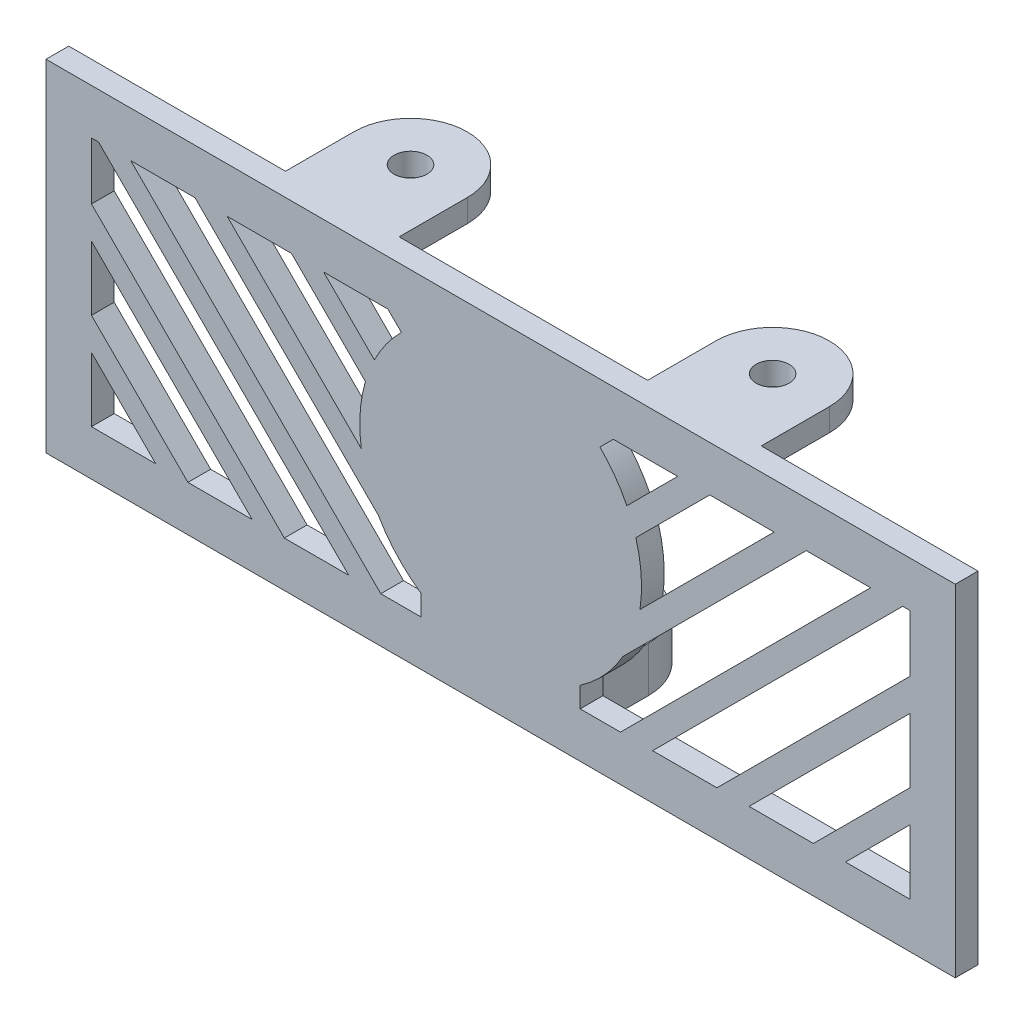
SolidWorks part; units mm, degrees
ref_plane "Front Plane" through (0, 0, 0) normal (0, 0, 1) x (1, 0, 0)
ref_plane "Top Plane" through (0, 0, 0) normal (0, 1, 0) x (1, 0, 0)
ref_plane "Right Plane" through (0, 0, 0) normal (1, 0, 0) x (0, 0, -1)
sketch "Sketch1" plane through (0, 0, 0) normal (0, 1, 0) x (1, 0, 0)
  line L0 (100.8063, 0) -> (100.8063, -127) construction
  line L1 (0, 0) -> (201.6125, 0)
  line L2 (0, 0) -> (0, -45.847)
  line L3 (0, -45.847) -> (34.944, -45.847)
  line L9 (19.05, -7.62) -> (182.5625, -7.62)
  line L10 (19.05, -7.62) -> (19.05, -38.2238)
  line L11 (19.05, -38.2238) -> (182.5625, -38.2238)
  line L12 (182.5625, -7.62) -> (182.5625, -38.2238)
  line L13 (60.344, -58.547) -> (73.2151, -58.547) construction
  line L14 (141.2685, -58.547) -> (171.549, -58.547) construction
  line L15 (74.2236, -72.4265) -> (74.2236, -91.8023) construction
  line L16 (127.3874, -72.4281) -> (127.3874, -64.5576) construction
  line L17 (166.6685, -45.847) -> (201.6125, -45.847)
  line L18 (182.5625, -22.9219) -> (-7.7585, -22.9219) construction
  line L22 (201.6125, 0) -> (201.6125, -45.847)
  line L29 (34.944, -45.847) -> (34.9441, -83.7692)
  line L30 (100.8063, -127) -> (100.8063, -142.2501) construction
  line L32 (166.6685, -45.847) -> (166.6685, -83.7692)
  line L34 (114.6874, -72.4281) -> (114.6874, -88.9176) construction
  line L35 (100.8063, -58.547) -> (112.2464, -58.547) construction
  line L36 (50.1841, -99.0092) -> (151.4284, -99.0092)
  line L37 (141.2685, -86.3092) -> (149.6169, -86.3092) construction
  circle A0 centre (60.344, -72.4265) radius 13.8795
  circle A1 centre (141.2685, -72.4281) radius 13.8811
  circle A2 centre (13.0969, -9.7139) radius 2.54
  circle A3 centre (188.5156, -9.7139) radius 2.54
  circle A4 centre (13.0969, -36.1299) radius 2.54
  circle A5 centre (188.5156, -36.1299) radius 2.54
  circle A10 centre (100.8063, -72.4281) radius 13.8811
  arc A23 (151.4284, -99.0092) -> (166.6685, -83.7692) centre (151.4285, -83.7692) ccw
  arc A24 (50.1841, -99.0092) -> (34.9441, -83.7692) centre (50.184, -83.7692) cw
  point P48 (166.6685, -99.0092)
  point P51 (34.9441, -99.0092)
  dimension "D7" = 27.759
  dimension "D16" = 5.08
  dimension "D33" = 27.7622
  dimension "D21" = 27.7622
  dimension "D22" = 15.24
  dimension "D1" = 201.6125
  dimension "D2" = 30.6038
  dimension "D3" = 163.5125
  dimension "D4" = 19.05
  dimension "D5" = 45.847
  dimension "D6" = 7.62
  dimension "D9" = 12.7
  dimension "D14" = 175.4187
  dimension "D15" = 87.7094
  dimension "D17" = 26.416
  dimension "D18" = 13.208
  dimension "D19" = 26.416
  dimension "D20" = 13.208
  dimension "D8" = 25.4
  dimension "D10" = 12.7
  dimension "D11" = 25.4
  dimension "D12" = 12.7
  dimension "D13" = 12.7
extrude "Boss-Extrude1" add sketch "Sketch1" along normal blind 5.08
sketch "Sketch3" plane through (0, 0, 198.0184) normal (0, 1, 0) x (-1, 0, 0)
  line L12 (-50.1841, -99.0092) -> (-151.4284, -99.0092) construction
  line L14 (-50.0063, -101.5492) -> (-151.6062, -101.5492)
  line L21 (-50.0063, -101.5492) -> (-50.0063, -99.0092)
  line L22 (-50.0063, -99.0092) -> (-151.6062, -99.0092)
  line L23 (-151.6062, -99.0092) -> (-151.6062, -101.5492)
  point P3 (-100.8063, -101.5492)
  point P7 (-100.8063, -99.0092)
  point P10 (-100.8063, -99.0092)
  dimension "D1" = 101.6
  dimension "D2" = 2.54
extrude "Boss-Extrude4" add sketch "Sketch3" against normal blind 38.1
sketch "Sketch7" plane through (0, 0, 99.0092) normal (0, 0, -1) x (1, 0, 0)
  line L1 (96.9962, 33.02) -> (104.6162, 33.02)
  line L2 (96.9962, 33.02) -> (96.9962, 38.1)
  line L3 (96.9962, 38.1) -> (104.6162, 38.1)
  line L4 (104.6162, 33.02) -> (104.6162, 38.1)
  line L7 (151.6062, 38.1) -> (151.6062, 0) construction
  line L9 (50.0063, 38.1) -> (151.6062, 38.1) construction
  dimension "D1" = 46.99
  dimension "D2" = 7.62
  dimension "D3" = 5.08
  dimension "D4" = 0
extrude "Boss-Extrude5" add sketch "Sketch7" along normal blind 11.43
fillet "Fillet5" 2 edges at (104.6162, -35.56, 87.5792) (96.9962, -35.56, 87.5792) type full round first side face at (104.6162, -35.56, 92.0242) second side face at (96.9962, -35.56, 92.0242) middle face at (100.8062, -35.56, 87.5792)
sketch "Sketch12" plane through (201.6125, 0, 0) normal (1, 0, 0) x (0, 0, -1)
  line L2 (0, 0) -> (-155.0308, 0)
  line L3 (0, 0) -> (0, 26.8372)
  line L4 (0, 26.8372) -> (-155.0308, 26.8372)
  line L5 (-155.0308, 0) -> (-155.0308, 26.8372)
sketch "Sketch14" plane through (0, 0, 99.0092) normal (0, 0, -1) x (-1, 0, 0)
  line L0 (199.3383, 310.1514) -> (657.3383, 310.1514) construction
  line L1 (-106.6923, -23.8525) -> (-108.1651, -25.3252)
  line L2 (-94.3545, -23.0235) -> (-92.9253, -24.8077)
  line L3 (-109.3118, -20.69) -> (-109.3118, -12.0094)
  line L4 (-92.301, -20.69) -> (-92.301, -12.0094)
  line L5 (-100.8062, -23.2208) -> (-99.5994, -22.3806)
  line L6 (-99.5994, -22.3806) -> (-99.5994, -18.3831)
  line L7 (-99.5994, -18.3831) -> (-94.428, -16.0226)
  line L8 (-94.428, -16.0226) -> (-95.2573, -18.7163)
  line L9 (-95.2573, -18.7163) -> (-98.169, -19.0875)
  line L10 (-98.169, -19.0875) -> (-98.169, -30.8772)
  line L11 (-98.169, -30.8772) -> (-98.1134, -30.8772)
  line L12 (-93.3803, -21.1933) -> (-93.3803, -12.3078)
  line L13 (-103.4991, -30.8772) -> (-103.4435, -30.8772)
  line L14 (-108.2322, -21.1933) -> (-108.2322, -12.3078)
  line L15 (-107.1845, -16.0226) -> (-106.3552, -18.7163)
  line L16 (-106.3552, -18.7163) -> (-103.4435, -19.0875)
  line L17 (-102.0131, -18.3831) -> (-107.1845, -16.0226)
  line L18 (-102.0131, -22.3806) -> (-102.0131, -18.3831)
  line L19 (-100.8062, -23.2208) -> (-102.0131, -22.3806)
  line L20 (-103.4435, -19.0875) -> (-103.4435, -30.8772)
  line L21 (-109.188, -24.2376) -> (-111.0162, -25.7334)
  line L22 (-110.6636, -21.8648) -> (-112.8137, -22.8431)
  line L23 (-90.6831, -21.2276) -> (-88.475, -22.0669)
  line L24 (-90.0847, -25.0658) -> (-92.0045, -23.6895)
  line L25 (-100.8062, -23.2208) -> (-100.8062, -7.3481) construction
  line L26 (-100.8062, -6.8497) -> (-100.8062, -4.1876) construction
  line L27 (-111.494, -19.1279) -> (-113.8252, -19.5092)
  line L28 (-111.5856, -16.3352) -> (-113.9368, -16.1074)
  line L29 (-110.9363, -13.5498) -> (-113.1458, -12.7144)
  line L30 (-109.6192, -11.0855) -> (-111.5415, -9.7126)
  line L31 (-107.6642, -8.9979) -> (-109.16, -7.1697)
  line L32 (-105.2914, -7.5223) -> (-106.2698, -5.3722)
  line L33 (-102.5545, -6.6919) -> (-102.9358, -4.3606)
  line L34 (-99.7619, -6.6003) -> (-99.5341, -4.2491)
  line L35 (-96.9764, -7.2496) -> (-96.141, -5.0401)
  line L36 (-94.5121, -8.5667) -> (-93.1392, -6.6444)
  line L37 (-92.4245, -10.5217) -> (-90.5963, -9.0259)
  line L38 (-90.9489, -12.8944) -> (-88.7988, -11.9161)
  line L39 (-90.1185, -15.6314) -> (-87.7873, -15.2501)
  line L40 (-90.0269, -18.424) -> (-87.6757, -18.6518)
  line L42 (-151.6062, -38.1) -> (-151.6062, 0) construction
  line L49 (-107.1004, -26.1926) -> (-108.4733, -28.1149) [skipped]
  line L50 (-104.6361, -27.5096) -> (-105.4715, -29.7192) [skipped]
  line L51 (-101.8506, -28.159) -> (-102.0784, -30.5102) [skipped]
  line L52 (-99.058, -28.0674) -> (-98.6767, -30.3986) [skipped]
  line L53 (-96.3211, -27.237) -> (-95.3427, -29.3871) [skipped]
  line L54 (-93.9483, -25.7614) -> (-92.4525, -27.5896) [skipped]
  line L55 (-90.6762, -21.2095) -> (-88.4667, -22.0449) [skipped]
  line L56 (-91.9933, -23.6738) -> (-90.071, -25.0466) [skipped]
  arc A0 (-108.1651, -25.3252) -> (-109.188, -24.2376) centre (-100.8062, -17.3796) cw
  arc A1 (-106.6923, -23.8525) -> (-109.3118, -20.69) centre (-120.3142, -32.4693) ccw
  arc A2 (-94.3545, -23.0235) -> (-92.301, -20.69) centre (-85.0837, -29.1115) cw
  arc A3 (-109.3118, -12.0094) -> (-100.8062, -6.8497) centre (-112.667, 3.112) ccw
  arc A4 (-92.301, -12.0094) -> (-100.8062, -6.8497) centre (-89.2554, 2.6009) cw
  arc A5 (-98.1134, -30.8772) -> (-93.3803, -21.1933) centre (-78.0697, -34.675) cw
  arc A6 (-93.3803, -12.3078) -> (-100.8062, -7.3481) centre (-90.4186, 0.1657) cw
  arc A7 (-108.2322, -12.3078) -> (-100.8062, -7.3481) centre (-111.1939, 0.1657) ccw
  arc A8 (-103.4991, -30.8772) -> (-108.2322, -21.1933) centre (-123.5428, -34.675) ccw
  arc A9 (-111.0162, -25.7334) -> (-112.8137, -22.8431) centre (-100.8062, -17.3796) cw
  arc A10 (-113.8252, -19.5092) -> (-113.9368, -16.1074) centre (-100.8062, -17.3796) cw
  arc A11 (-110.6636, -21.8648) -> (-111.494, -19.1279) centre (-100.8062, -17.3796) cw
  arc A12 (-111.5856, -16.3352) -> (-110.9363, -13.5498) centre (-100.8062, -17.3796) cw
  arc A13 (-113.1458, -12.7144) -> (-111.5415, -9.7126) centre (-100.8062, -17.3796) cw
  arc A14 (-109.16, -7.1697) -> (-106.2698, -5.3722) centre (-100.8062, -17.3796) cw
  arc A15 (-109.6192, -11.0855) -> (-107.6642, -8.9979) centre (-100.8062, -17.3796) cw
  arc A16 (-102.9358, -4.3606) -> (-99.5341, -4.2491) centre (-100.8062, -17.3796) cw
  arc A17 (-105.2914, -7.5223) -> (-102.5545, -6.6919) centre (-100.8062, -17.3796) cw
  arc A18 (-96.141, -5.0401) -> (-93.1392, -6.6444) centre (-100.8062, -17.3796) cw
  arc A19 (-99.7619, -6.6003) -> (-96.9764, -7.2496) centre (-100.8062, -17.3796) cw
  arc A20 (-94.5121, -8.5667) -> (-92.4245, -10.5217) centre (-100.8062, -17.3796) cw
  arc A21 (-90.5963, -9.0259) -> (-88.7988, -11.9161) centre (-100.8062, -17.3796) cw
  arc A22 (-90.9489, -12.8944) -> (-90.1185, -15.6314) centre (-100.8062, -17.3796) cw
  arc A23 (-87.7873, -15.2501) -> (-87.6757, -18.6518) centre (-100.8062, -17.3796) cw
  arc A24 (-90.0269, -18.424) -> (-90.6831, -21.2276) centre (-100.8062, -17.3796) cw
  arc A25 (-88.475, -22.0669) -> (-90.0847, -25.0658) centre (-100.8062, -17.3796) cw
  arc A26 (-92.0045, -23.6895) -> (-92.9253, -24.8077) centre (-100.8062, -17.3796) cw
  point P16 (-100.8062, -6.8497)
  point P101 (-100.8062, -17.3796)
  dimension "D3" = 50.8
  dimension "D1" = 2.0828
  dimension "D2" = 2.286
  dimension "D4" = 50.8
  dimension "D5" = 2.3622
  dimension "D6" = 2.3622
  dimension "D11" = 3.4036
  dimension "D12" = 3.4036
  dimension "D13" = 12
extrude "Boss-Extrude6" add sketch "Sketch14" against normal blind 2.54 contours L13 L20 L16 L15 L17 L18 L19 L5 L6 L7 L8 L9 L10 L11 A5 L12 A6 A7 L14 A8 | L40 A23 L39 A22 L38 A21 L37 A20 L36 A18 L35 A19 L34 A16 L33 A17 L32 A14 L31 A15 L30 A13 L29 A12 L28 A10 L27 A11 L22 A9 L21 A0 L1 A1 L3 A3 A4 L4 A2 L2 A26 L24 A25 L23 A24
sketch "Sketch15" plane through (0, 0, 0) normal (0, -1, 0) x (1, 0, 0)
  line L0 (121.0374, 88.8492) -> (121.0374, 58.7984) construction
  line L2 (100.8063, 72.4281) -> (100.8063, 116.3624) construction
  line L3 (114.6873, 88.8492) -> (114.6873, 96.4692)
  line L4 (151.6062, 96.4692) -> (50.0063, 96.4692) construction
  line L5 (127.3874, 88.8492) -> (127.3874, 96.4692)
  line L6 (127.3874, 96.4692) -> (114.6873, 96.4692)
  line L7 (74.2251, 96.4692) -> (86.9252, 96.4692)
  line L8 (74.2251, 88.8492) -> (74.2251, 96.4692)
  line L9 (86.9252, 88.8492) -> (86.9252, 96.4692)
  line L10 (100.8063, 72.4281) -> (121.0374, 88.8492) construction
  line L11 (100.8063, 72.4281) -> (80.5752, 88.8492) construction
  line L12 (100.8063, 72.4281) -> (135.1371, 72.4281) construction
  circle A2 centre (121.0374, 88.8492) radius 1.8415
  arc A3 (114.6873, 88.8492) -> (127.3874, 88.8492) centre (121.0374, 88.8492) ccw
  arc A4 (86.9252, 88.8492) -> (74.2251, 88.8492) centre (80.5752, 88.8492) cw
  circle A5 centre (80.5752, 88.8492) radius 1.8415
  dimension "D1" = 39.065
  dimension "D4" = 3.683
  dimension "D3" = 20.2311
extrude "Boss-Extrude7" add sketch "Sketch15" along normal blind 2.54
sketch "Sketch19" plane through (0, 0, 0) normal (0, -1, 0) x (1, 0, 0)
  circle A0 centre (80.5752, 88.8492) radius 1.8415
  circle A1 centre (121.0374, 88.8492) radius 1.8415
  dimension "D1" = 3.683
  dimension "D2" = 3.683
extrude "Cut-Extrude3" cut sketch "Sketch19" against normal blind 5.08
extrude "Cut-Extrude4" cut sketch "Sketch12" against normal through all
sketch "Sketch21" plane through (0, 0, 99.0092) normal (0, 0, 1) x (1, 0, 0)
  line L0 (55.0863, -33.02) -> (55.0863, -25.8358)
  line L1 (55.0863, -5.08) -> (55.8831, -5.08)
  line L2 (50.0063, -38.1) -> (50.0063, 0) construction
  line L3 (50.0063, 0) -> (151.6062, 0) construction
  line L4 (55.0863, -33.02) -> (62.2705, -33.02)
  line L5 (91.9162, -33.02) -> (91.9162, -30.7371)
  line L6 (146.5263, -5.08) -> (145.7294, -5.08)
  line L7 (96.9962, -38.1) -> (96.9962, -33.02) construction
  line L8 (109.6962, -33.02) -> (114.1973, -33.02)
  line L9 (146.5263, -33.02) -> (146.5263, -25.8358)
  line L10 (139.342, -33.02) -> (146.5263, -25.8358)
  line L11 (50.0063, -38.1) -> (151.6062, -38.1) construction
  line L12 (151.6062, -38.1) -> (151.6062, 0) construction
  line L13 (109.6962, -33.02) -> (109.6962, -30.7371)
  line L14 (104.6162, -33.02) -> (104.6162, -38.1) construction
  line L15 (135.7499, -33.02) -> (146.5263, -22.2437)
  line L16 (128.5657, -33.02) -> (146.5263, -15.0595)
  line L17 (124.1768, -5.08) -> (115.9162, -13.3406)
  line L18 (124.9736, -33.02) -> (146.5263, -11.4674)
  line L19 (117.7894, -33.02) -> (145.7294, -5.08)
  line L20 (114.1973, -33.02) -> (142.1373, -5.08)
  line L21 (120.5847, -5.08) -> (114.9079, -10.7568)
  line L22 (134.9531, -5.08) -> (114.4674, -25.5657)
  line L23 (131.361, -5.08) -> (116.3743, -20.0667)
  line L24 (113.4005, -5.08) -> (111.8988, -6.5817)
  line L25 (100.8063, -17.7484) -> (100.8063, 4.9484) construction
  line L26 (62.2705, -33.02) -> (55.0863, -25.8358)
  line L27 (65.8626, -33.02) -> (55.0863, -22.2437)
  line L28 (73.0468, -33.02) -> (55.0863, -15.0595)
  line L29 (76.6389, -33.02) -> (55.0863, -11.4674)
  line L30 (83.8231, -33.02) -> (55.8831, -5.08)
  line L31 (87.4152, -33.02) -> (59.4752, -5.08)
  line L32 (66.6594, -5.08) -> (87.1451, -25.5657)
  line L33 (70.2515, -5.08) -> (85.2382, -20.0667)
  line L34 (77.4357, -5.08) -> (85.6963, -13.3406)
  line L35 (81.0278, -5.08) -> (86.7046, -10.7568)
  line L36 (88.212, -5.08) -> (89.7137, -6.5817)
  line L37 (120.5847, -5.08) -> (113.4005, -5.08)
  line L38 (131.361, -5.08) -> (124.1768, -5.08)
  line L39 (117.7894, -33.02) -> (124.9736, -33.02)
  line L40 (142.1373, -5.08) -> (134.9531, -5.08)
  line L41 (128.5657, -33.02) -> (135.7499, -33.02)
  line L42 (146.5263, -11.4674) -> (146.5263, -5.08)
  line L43 (139.342, -33.02) -> (146.5263, -33.02)
  line L44 (146.5263, -22.2437) -> (146.5263, -15.0595)
  line L45 (81.0278, -5.08) -> (88.212, -5.08)
  line L46 (70.2515, -5.08) -> (77.4357, -5.08)
  line L47 (59.4752, -5.08) -> (66.6594, -5.08)
  line L48 (87.4152, -33.02) -> (91.9162, -33.02)
  line L49 (76.6389, -33.02) -> (83.8231, -33.02)
  line L50 (55.0863, -11.4674) -> (55.0863, -5.08)
  line L51 (55.0863, -22.2437) -> (55.0863, -15.0595)
  line L52 (65.8626, -33.02) -> (73.0468, -33.02)
  arc A0 (91.9162, -30.7371) -> (87.1451, -25.5657) centre (100.8063, -17.7484) cw
  arc A1 (111.8988, -6.5817) -> (114.9079, -10.7568) centre (100.8063, -17.7484) cw
  arc A2 (115.9162, -13.3406) -> (116.3743, -20.0667) centre (100.8063, -17.7484) cw
  arc A3 (114.4674, -25.5657) -> (109.6962, -30.7371) centre (100.8063, -17.7484) cw
  arc A4 (86.7046, -10.7568) -> (89.7137, -6.5817) centre (100.8063, -17.7484) cw
  arc A5 (85.2382, -20.0667) -> (85.6963, -13.3406) centre (100.8063, -17.7484) cw
  dimension "D4" = 5.08
  dimension "D1" = 5.08
  dimension "D2" = 5.08
  dimension "D3" = 5.08
  dimension "D5" = 5.08
  dimension "D6" = 5.08
  dimension "D7" = 5.08
  dimension "D8" = 2.54
  dimension "D9" = 5.08
  dimension "D10" = 2.54
  dimension "D11" = 45
  dimension "D12" = 5.08
  dimension "D13" = 2.54
  dimension "D14" = 5.08
  dimension "D15" = 2.54
  dimension "D16" = 5.08
  dimension "D17" = 2.54
  dimension "D18" = 5.08
extrude "Cut-Extrude5" cut sketch "Sketch21" against normal blind 2.54
fillet "Fillet6" radius 2.54 2 edges at (151.6062, -19.05, 99.0092) (50.0063, -19.05, 99.0092)
sketch "Sketch22" plane through (0, -33.02, 0) normal (0, 1, 0) x (1, 0, 0)
  line L0 (100.8063, -96.4692) -> (100.8063, -88.8492) construction
  line L1 (114.6873, -96.4692) -> (86.9252, -96.4692) construction
  line L2 (94.4563, -96.4692) -> (94.4563, -88.8492)
  line L3 (107.1563, -96.4692) -> (107.1563, -88.8492)
  line L4 (80.5752, -88.8492) -> (121.2071, -88.8492) construction
  line L5 (94.4563, -96.4692) -> (107.1563, -96.4692)
  arc A1 (107.1563, -88.8492) -> (94.4563, -88.8492) centre (100.8063, -88.8492) ccw
  point P4 (100.8063, -92.6592)
  dimension "D1" = 6.35
extrude "Boss-Extrude8" add sketch "Sketch22" against normal blind 5.08
sketch "Sketch23" plane through (0, -33.02, 0) normal (0, 1, 0) x (1, 0, 0)
  circle A0 centre (100.8063, -88.8492) radius 1.8415
  dimension "D1" = 3.683
extrude "Cut-Extrude6" cut sketch "Sketch23" against normal through all both and the other way through all
sketch "Sketch25" plane through (0, 0, 99.0092) normal (0, 0, 1) x (1, 0, 0)
  circle A0 centre (100.8063, -17.7484) radius 14.4989
extrude "Cut-Extrude7" cut sketch "Sketch25" along normal up to surface (2.54 mm away) up to face at (100.8062, -20.5479, 101.5492)
sketch "Sketch26" plane through (0, 0, 0) normal (0, 1, 0) x (1, 0, 0)
  line L0 (52.5463, -99.0092) -> (149.0663, -99.0092) construction
  line L1 (50.0063, -96.4692) -> (52.8184, -96.4692)
  line L2 (50.0063, -96.4692) -> (50.0063, -99.0092)
  line L3 (50.0063, -99.0092) -> (52.8184, -99.0092)
  line L4 (52.8184, -96.4692) -> (52.8184, -99.0092)
  line L5 (151.6062, -96.4692) -> (148.3631, -96.4692)
  line L6 (151.6062, -96.4692) -> (151.6062, -99.0092)
  line L7 (151.6062, -99.0092) -> (148.3631, -99.0092)
  line L8 (148.3631, -96.4692) -> (148.3631, -99.0092)
extrude "Boss-Extrude9" add sketch "Sketch26" against normal up to surface (38.1 mm away) up to face at (100.8063, -38.1, 90.6907)
equation "\"D15@Sketch1\"=\"D14@Sketch1\"/2"
equation "\"D18@Sketch1\"=\"D17@Sketch1\"/2"
equation "\"D19@Sketch1\"=\"D17@Sketch1\""
equation "\"D20@Sketch1\"=\"D18@Sketch1\""
